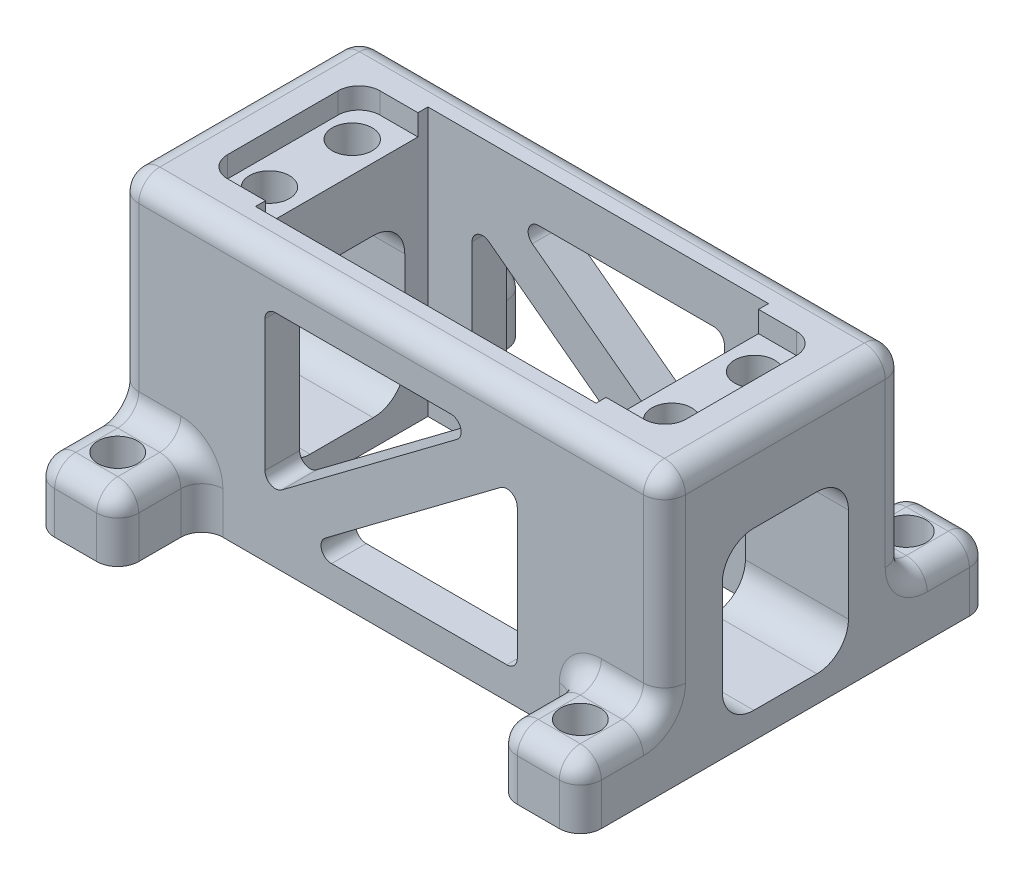
SolidWorks part; units mm, degrees
ref_plane "Front Plane" through (0, 0, 0) normal (0, 0, 1) x (1, 0, 0)
ref_plane "Top Plane" through (0, 0, 0) normal (0, 1, 0) x (1, 0, 0)
ref_plane "Right Plane" through (0, 0, 0) normal (1, 0, 0) x (0, 0, -1)
sketch "Sketch1" plane through (0, 0, 0) normal (0, 1, 0) x (1, 0, 0)
  line L9 (-20.574, 10.414) -> (20.574, 10.414)
  line L10 (-20.574, 10.414) -> (-20.574, -10.414)
  line L11 (-20.574, -10.414) -> (20.574, -10.414)
  line L12 (20.574, 10.414) -> (20.574, -10.414)
  line L13 (-20.574, 10.414) -> (20.574, -10.414) construction
  line L14 (-20.574, -10.414) -> (20.574, 10.414) construction
  line L15 (-33.02, 14.605) -> (33.02, 14.605)
  line L16 (-33.02, 14.605) -> (-33.02, -14.605)
  line L17 (-33.02, -14.605) -> (33.02, -14.605)
  line L18 (33.02, 14.605) -> (33.02, -14.605)
  line L19 (-33.02, 14.605) -> (33.02, -14.605) construction
  line L20 (-33.02, -14.605) -> (33.02, 14.605) construction
  point P0 (0, 0)
  point P6 (0, 0)
  dimension "D1" = 41.148
  dimension "D2" = 20.828
  dimension "D3" = 66.04
  dimension "D4" = 29.21
extrude "Boss-Extrude1" add sketch "Sketch1" along normal blind 32.385
sketch "Sketch2" plane through (0, 32.385, 0) normal (0, 1, 0) x (1, 0, 0)
  line L0 (0, 14.605) -> (0, -14.605) construction
  line L1 (33.02, 14.605) -> (-33.02, 14.605) construction
  line L2 (-33.02, -14.605) -> (33.02, -14.605) construction
  line L3 (20.574, -10.414) -> (20.574, 10.414) construction
  line L4 (20.574, 9.2075) -> (25.146, 9.2075)
  line L5 (20.574, 9.2075) -> (20.574, -9.2075)
  line L6 (20.574, -9.2075) -> (25.146, -9.2075)
  line L7 (27.686, 6.6675) -> (27.686, -6.6675)
  line L8 (-20.574, -9.2075) -> (-25.146, -9.2075)
  line L9 (-27.686, 6.6675) -> (-27.686, -6.6675)
  line L10 (-20.574, 9.2075) -> (-25.146, 9.2075)
  line L11 (-20.574, 9.2075) -> (-20.574, -9.2075)
  arc A0 (25.146, -9.2075) -> (27.686, -6.6675) centre (25.146, -6.6675) ccw
  arc A1 (25.146, 9.2075) -> (27.686, 6.6675) centre (25.146, 6.6675) cw
  arc A2 (-25.146, -9.2075) -> (-27.686, -6.6675) centre (-25.146, -6.6675) cw
  arc A3 (-25.146, 9.2075) -> (-27.686, 6.6675) centre (-25.146, 6.6675) ccw
  point P12 (20.574, 0)
  point P13 (20.574, 0)
  point P18 (27.686, 9.2075)
  dimension "D3" = 2.54
  dimension "D1" = 18.415
  dimension "D2" = 7.112
extrude "Cut-Extrude1" cut sketch "Sketch2" against normal blind 2.54
sketch "Sketch3" plane through (0, 29.845, 0) normal (0, 1, 0) x (1, 0, 0)
  line L0 (24.3, 9.2075) -> (24.3, -9.2075) construction
  line L1 (25.146, 9.2075) -> (20.574, 9.2075) construction
  line L2 (20.574, -9.2075) -> (25.146, -9.2075) construction
  line L3 (0, 10.414) -> (0, -10.414) construction
  line L6 (24.3, 5) -> (24.3, -5)
  line L7 (20.574, 10.414) -> (-20.574, 10.414) construction
  line L8 (-20.574, -10.414) -> (20.574, -10.414) construction
  line L9 (-24.3, 9.2075) -> (-24.3, -9.2075) construction
  line L10 (-24.3, 5) -> (-24.3, -5)
  circle A0 centre (24.3, 5) radius 2.413
  circle A1 centre (24.3, -5) radius 2.413
  circle A2 centre (-24.3, -5) radius 2.413
  circle A3 centre (-24.3, 5) radius 2.413
  point P16 (24.3, 0)
  point P17 (24.3, 0)
  dimension "D2" = 4.826
  dimension "D3" = 4.826
  dimension "D1" = 10
  dimension "D4" = 48.6
extrude "Cut-Extrude2" cut sketch "Sketch3" against normal blind 10.16 contours A2 | A0 | A1 | A3 region at (25.958, 29.845, 3.342) region at (22.642, 29.845, -6.658) region at (-22.642, 29.845, 3.342)
sketch "Sketch4" plane through (0, 0, 0) normal (0, -1, 0) x (1, 0, 0)
  line L0 (0, 14.605) -> (0, -14.605) construction
  line L1 (-33.02, 14.605) -> (-22.86, 14.605)
  line L2 (-33.02, 14.605) -> (-33.02, 24.765)
  line L3 (-33.02, 24.765) -> (-22.86, 24.765)
  line L4 (-22.86, 14.605) -> (-22.86, 24.765)
  line L5 (-33.02, -14.605) -> (-22.86, -14.605)
  line L6 (-33.02, -14.605) -> (-33.02, -24.765)
  line L7 (-33.02, -24.765) -> (-22.86, -24.765)
  line L8 (-22.86, -14.605) -> (-22.86, -24.765)
  line L9 (-33.02, 14.605) -> (33.02, 14.605) construction
  line L10 (33.02, -14.605) -> (-33.02, -14.605) construction
  line L11 (33.02, -24.765) -> (22.86, -24.765)
  line L12 (22.86, -14.605) -> (22.86, -24.765)
  line L13 (33.02, -14.605) -> (22.86, -14.605)
  line L14 (33.02, -14.605) -> (33.02, -24.765)
  line L15 (33.02, 24.765) -> (22.86, 24.765)
  line L16 (22.86, 14.605) -> (22.86, 24.765)
  line L17 (33.02, 14.605) -> (22.86, 14.605)
  line L18 (33.02, 14.605) -> (33.02, 24.765)
  line M11 (33.02, 14.605) -> (-33.02, 14.605)
  dimension "D1" = 10.16
  dimension "D2" = 10.16
  dimension "D3" = 10.16
  dimension "D4" = 10.16
extrude "Boss-Extrude2" add sketch "Sketch4" against normal blind 7.62 contours L18 L15 L16 M11 | L2 L3 L4 L1 | L6 L7 L8 L5 | L12 L11 L14 L13 region at (27.94, 0, 19.685)
sketch "Sketch5" plane through (0, 0, 0) normal (0, -1, 0) x (1, 0, 0)
  line L0 (-33.02, 19.685) -> (33.02, 19.685) construction
  line L1 (-33.02, -24.765) -> (-33.02, 24.765) construction
  line L2 (33.02, 24.765) -> (33.02, -24.765) construction
  line L3 (-33.02, -19.685) -> (33.02, -19.685) construction
  line L4 (27.94, 24.765) -> (27.94, -24.765) construction
  line L5 (33.02, 24.765) -> (22.86, 24.765) construction
  line L6 (33.02, -24.765) -> (22.86, -24.765) construction
  line L7 (-27.94, -24.765) -> (-27.94, 24.765) construction
  line L8 (-33.02, -24.765) -> (-22.86, -24.765) construction
  line L9 (-33.02, 24.765) -> (-22.86, 24.765) construction
  line L10 (-22.86, -14.605) -> (-22.86, -24.765) construction
  line L11 (-22.86, 14.605) -> (-22.86, 24.765) construction
  circle A0 centre (27.94, 19.685) radius 2.3876
  circle A1 centre (27.94, -19.685) radius 2.3876
  circle A2 centre (-27.94, -19.685) radius 2.3876
  circle A3 centre (-27.94, 19.685) radius 2.3876
  point P30 (-22.86, -19.685)
  point P33 (-22.86, 19.685)
  dimension "D3" = 4.7752
  dimension "D4" = 4.7752
  dimension "D5" = 4.7752
  dimension "D6" = 4.7752
extrude "Cut-Extrude3" cut sketch "Sketch5" against normal through all contours A3 | A0 | A2 | A1
fillet "Fillet1" radius 2.54 36 edges at (22.86, 3.81, -14.605) (33.02, 7.62, -19.685) (-22.86, 3.81, -14.605) (-33.02, 7.62, 19.685) (33.02, 7.62, 19.685) (-33.02, 32.385, 0) (33.02, 32.385, 0) (33.02, 3.81, -24.765) (22.86, 3.81, -24.765) (22.86, 7.62, -19.685) (27.94, 7.62, -24.765) (27.94, 7.62, -14.605) (0, 32.385, -14.605) (33.02, 20.0025, -14.605) (-22.86, 3.81, -24.765) (-33.02, 3.81, -24.765) (-27.94, 7.62, -24.765) (-22.86, 7.62, -19.685) (-27.94, 7.62, -14.605) (-33.02, 7.62, -19.685) (-33.02, 20.0025, -14.605) (-22.86, 3.81, 24.765) (-33.02, 3.81, 24.765) (22.86, 3.81, 24.765) (33.02, 3.81, 24.765) (-27.94, 7.62, 24.765) (27.94, 7.62, 24.765) (22.86, 7.62, 19.685) (-22.86, 7.62, 19.685) (22.86, 3.81, 14.605) (-22.86, 3.81, 14.605) (-27.94, 7.62, 14.605) (27.94, 7.62, 14.605) (0, 32.385, 14.605) (33.02, 20.0025, 14.605) (-33.02, 20.0025, 14.605)
sketch "Sketch6" plane through (33.02, 0, 0) normal (1, 0, 0) x (0, 0, -1)
  line L1 (-3.81, 22.225) -> (3.81, 22.225)
  line L2 (-7.62, 18.415) -> (-7.62, 6.985)
  line L3 (-3.81, 3.175) -> (3.81, 3.175)
  line L4 (7.62, 18.415) -> (7.62, 6.985)
  line L5 (-7.62, 22.225) -> (7.62, 3.175) construction
  line L6 (-7.62, 3.175) -> (7.62, 22.225) construction
  line L7 (0, 0) -> (0, 29.845) construction
  line L8 (12.065, 29.845) -> (-12.065, 29.845) construction
  arc A0 (3.81, 3.175) -> (7.62, 6.985) centre (3.81, 6.985) ccw
  arc A1 (-7.62, 6.985) -> (-3.81, 3.175) centre (-3.81, 6.985) ccw
  arc A2 (3.81, 22.225) -> (7.62, 18.415) centre (3.81, 18.415) cw
  arc A3 (-3.81, 22.225) -> (-7.62, 18.415) centre (-3.81, 18.415) ccw
  point P0 (0, 12.7)
  dimension "D4" = 3.81
  dimension "D2" = 19.05
  dimension "D3" = 15.24
  dimension "D5" = 3.175
extrude "Cut-Extrude4" cut sketch "Sketch6" against normal through all contours A3 L2 A1 L3 A0 L4 A2 L1
sketch "Sketch9" plane through (0, 0, -14.605) normal (0, 0, -1) x (-1, 0, 0)
  line L0 (-20.32, 0) -> (20.32, 0) construction
  line L1 (-13.97, 26.67) -> (7.1967, 26.67)
  line L2 (-15.24, 25.4) -> (-15.24, 9.525)
  line L3 (-7.1967, 3.81) -> (13.97, 3.81)
  line L4 (15.24, 20.955) -> (15.24, 5.08)
  line L5 (-15.24, 26.67) -> (15.24, 3.81) construction
  line L6 (-15.24, 3.81) -> (15.24, 26.67) construction
  line L7 (0, 0) -> (0, 32.385) construction
  line L8 (-30.48, 32.385) -> (30.48, 32.385) construction
  line L9 (-7.9587, 6.096) -> (13.208, 21.971)
  line L10 (7.9587, 24.384) -> (-13.208, 8.509)
  line L11 (-4.919, 14.7258) -> (-1.871, 10.6618) construction
  arc A0 (13.208, 21.971) -> (15.24, 20.955) centre (13.97, 20.955) cw
  arc A1 (13.97, 3.81) -> (15.24, 5.08) centre (13.97, 5.08) ccw
  arc A2 (-7.9587, 6.096) -> (-7.1967, 3.81) centre (-7.1967, 5.08) ccw
  arc A3 (-13.208, 8.509) -> (-15.24, 9.525) centre (-13.97, 9.525) cw
  arc A4 (7.9587, 24.384) -> (7.1967, 26.67) centre (7.1967, 25.4) ccw
  arc A5 (-13.97, 26.67) -> (-15.24, 25.4) centre (-13.97, 25.4) ccw
  point P0 (0, 15.24)
  point P18 (-3.395, 12.6938)
  point P33 (0, 0)
  dimension "D5" = 1.27
  dimension "D1" = 3.81
  dimension "D2" = 30.48
  dimension "D3" = 22.86
  dimension "D4" = 5.08
extrude "Cut-Extrude5" cut sketch "Sketch9" against normal up to next contours L1 A4 L10 A3 L2 A5 | L9 A0 L4 A1 L3 A2
sketch "Sketch10" plane through (0, 0, 14.605) normal (0, 0, 1) x (1, 0, 0)
  line L0 (0, 0) -> (0, 29.845) construction
  line L1 (30.48, 29.845) -> (-30.48, 29.845) construction
  line L2 (-20.32, 0) -> (20.32, 0) construction
  line L3 (-13.97, 26.67) -> (7.1967, 26.67)
  line L4 (-15.24, 25.4) -> (-15.24, 9.525)
  line L5 (-7.1967, 3.81) -> (13.97, 3.81)
  line L6 (15.24, 20.955) -> (15.24, 5.08)
  line L7 (-15.24, 26.67) -> (15.24, 3.81) construction
  line L8 (-15.24, 3.81) -> (15.24, 26.67) construction
  line L9 (-7.9587, 6.096) -> (13.208, 21.971)
  line L10 (-13.208, 8.509) -> (7.9587, 24.384)
  line L11 (-3.3383, 9.5613) -> (-6.3863, 13.6253) construction
  arc A0 (-7.9587, 6.096) -> (-7.1967, 3.81) centre (-7.1967, 5.08) ccw
  arc A1 (13.97, 3.81) -> (15.24, 5.08) centre (13.97, 5.08) ccw
  arc A2 (13.208, 21.971) -> (15.24, 20.955) centre (13.97, 20.955) cw
  arc A3 (7.9587, 24.384) -> (7.1967, 26.67) centre (7.1967, 25.4) ccw
  arc A4 (-13.208, 8.509) -> (-15.24, 9.525) centre (-13.97, 9.525) cw
  arc A5 (-13.97, 26.67) -> (-15.24, 25.4) centre (-13.97, 25.4) ccw
  point P5 (0, 15.24)
  point P18 (-4.8623, 11.5933)
  dimension "D5" = 1.27
  dimension "D1" = 30.48
  dimension "D2" = 22.86
  dimension "D3" = 3.81
  dimension "D4" = 5.08
extrude "Cut-Extrude6" cut sketch "Sketch10" against normal up to next contours A2 L9 A0 L5 A1 L6 | L3 A3 L10 A4 L4 A5 region at (6.607, 10.3777, 14.605)
